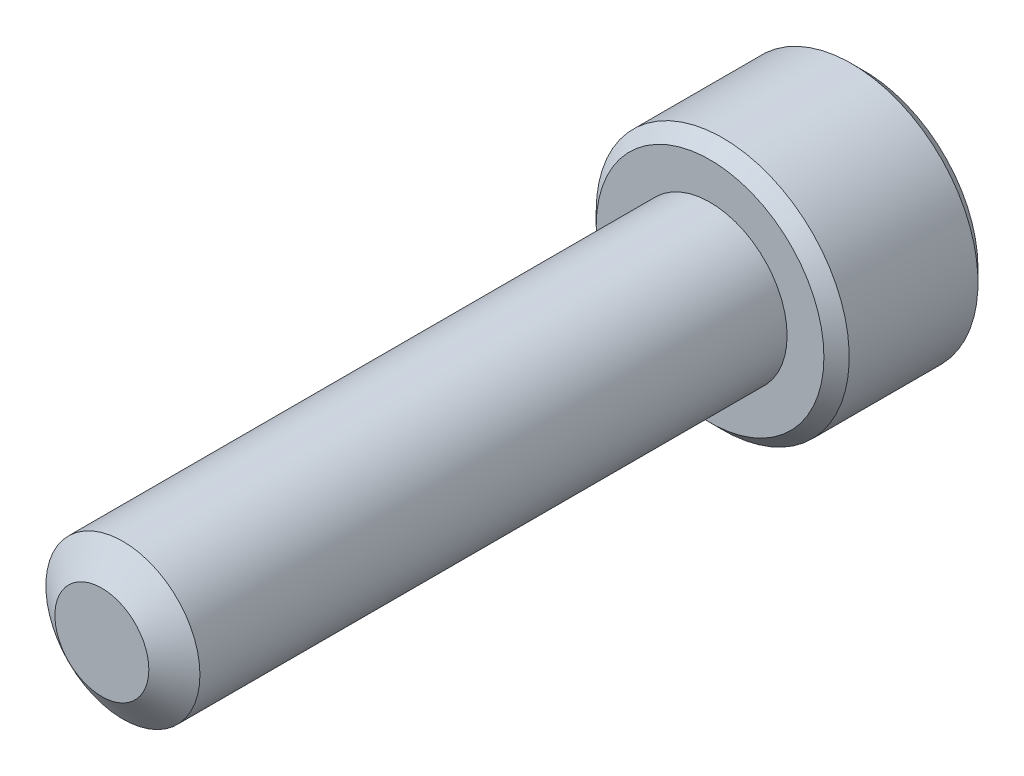
SolidWorks part; units mm, degrees
material "Plain Carbon Steel"
ref_plane "Front Plane" through (0, 0, 0) normal (0, 0, 1) x (1, 0, 0)
ref_plane "Top Plane" through (0, 0, 0) normal (0, 1, 0) x (1, 0, 0)
ref_plane "Right Plane" through (0, 0, 0) normal (1, 0, 0) x (0, 0, -1)
sketch "Sketch1" plane through (0, 0, 0) normal (0, 0, 1) x (1, 0, 0)
  circle A0 centre (0, 0) radius 2.413
  dimension "OD" = 4.826
extrude "Extrude1" add sketch "Sketch1" against normal blind 19.05
sketch "Sketch2" plane through (0, 0, 0) normal (0, 0, 1) x (1, 0, 0)
  circle A0 centre (0, 0) radius 2.413 construction
  circle A1 centre (0, 0) radius 2.413
curve "Helix/Spiral1" [suppressed] pitch 1.0583 height 20.1083 turns 19 parameters "pitch"=1.0583
sketch "Sketch3" plane through (0, 0, 0) normal (1, 0, 0) x (0, 0, -1)
  line L0 (-0.926, 2.413) -> (-0.5292, 1.7256)
  line L1 (-0.5292, 1.7256) -> (-0.3969, 1.7256)
  line L2 (-0.3969, 1.7256) -> (0, 2.413)
  line L3 (-0.926, 2.413) -> (0, 2.413)
  line L4 (-0.463, 2.413) -> (-0.463, 1.7256) construction
  line L5 (-0.7276, 2.0693) -> (-0.1984, 2.0693) construction
  line L6 (0, 2.413) -> (0, -2.413) construction
  dimension "D1" = 0.1323
  dimension "D2" = 0.5292
  dimension "D3" = 60
sweep "Cut-Sweep1" [suppressed] cut profiles "Sketch3" path "Helix/Spiral1"
sketch "Sketch4" plane through (0, 0, 0) normal (1, 0, 0) x (0, 0, -1)
  line L0 (0.6592, 2.413) -> (0, 1.4716)
  line L1 (0, 1.4716) -> (0, 2.413)
  line L2 (0.6592, 2.413) -> (0, 2.413)
  line L3 (-0.926, 2.413) -> (0, 2.413) construction
  line L4 (0, 0) -> (7.0209, 0) construction
  dimension "D1" = 55
  dimension "D2" = 0.254
revolve "Cut-Revolve1" cut sketch "Sketch4" angle 360 about L4
sketch "Sketch5" [suppressed] plane through (0, 0, 0) normal (1, 0, 0) x (0, 0, -1)
  line L0 (19.05, -1.7471) -> (19.05, 1.7217) construction
  line L1 (19.05, 2.54) -> (87.4327, 2.54)
  line L2 (19.05, 2.54) -> (19.05, 0)
  line L3 (19.05, 0) -> (87.3125, 0)
  line L4 (87.3125, 2.2098) -> (87.3125, 0)
  line L5 (87.4327, 2.54) -> (87.3125, 2.2098)
  line L6 (0, 0) -> (9.9695, 0) construction
  point P3 (87.3125, 2.54)
  point P10 (87.3125, 2.54)
  dimension "D1" = 0.3302
  dimension "Thread min" = 87.3125
  dimension "D2" = 0.127
  dimension "D3" = 20
revolve "partially thread" [suppressed] add sketch "Sketch5" angle 360 about L6
sketch "Sketch6" plane through (0, 0, -19.05) normal (0, 0, -1) x (-1, 0, 0)
  circle A0 centre (0, 0) radius 3.9624
  dimension "head dia" = 7.9248
extrude "Extrude2" add sketch "Sketch6" along normal blind 4.826
sketch "Sketch7" plane through (0, 0, -23.876) normal (0, 0, -1) x (-1, 0, 0)
  line L1 (0, 2.2914) -> (-1.9844, 1.1457)
  line L2 (-1.9844, 1.1457) -> (-1.9844, -1.1457)
  line L3 (-1.9844, -1.1457) -> (0, -2.2914)
  line L4 (0, -2.2914) -> (1.9844, -1.1457)
  line L5 (1.9844, -1.1457) -> (1.9844, 1.1457)
  line L6 (1.9844, 1.1457) -> (0, 2.2914)
  circle A0 centre (0, 0) radius 1.9844 construction
  dimension "hex dia" = 3.9688
extrude "Cut-Extrude1" cut sketch "Sketch7" against normal blind 2.9766
sketch "Sketch8" plane through (0, 0, -23.876) normal (0, 0, -1) x (-1, 0, 0)
  circle A0 centre (0, 0) radius 2.2914
extrude "Cut-Extrude2" cut sketch "Sketch8" against normal through all draft 45
chamfer "Chamfer1" distance 0.3962 angle 45 2 edges at (-3.9624, 0, -23.876) (-3.9624, 0, -19.05)
sketch "Sketch9" plane through (0, 0, 0) normal (1, 0, 0) x (0, 0, -1)
  line L0 (0, 2.413) -> (0, -2.413) construction
  line L1 (5.8208, 2.413) -> (5.8208, -2.413) construction
  dimension "D1" = 5.8208
equation "\"D3@Helix/Spiral1\" = \"screw length@Extrude1\"+\"pitch@Helix/Spiral1\""
equation "\"D1@Sketch3\" = \"pitch@Helix/Spiral1\"*.125"
equation "\"D2@Sketch3\" = \"pitch@Helix/Spiral1\"*.5"
equation "\"D1@Cut-Extrude1\" = \"hex dia@Sketch7\"*.75"
equation "\"D1@Chamfer1\" = \"head dia@Sketch6\"*.05"
equation "\"D1@Sketch9\" = \"pitch@Helix/Spiral1\"*5.5"
